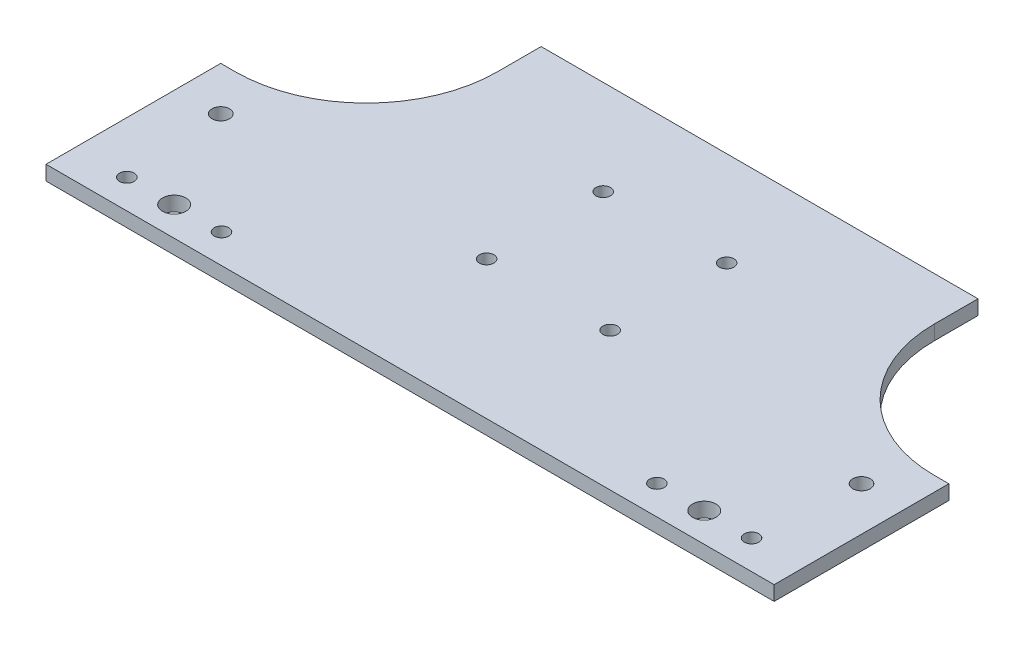
SolidWorks part; units mm, degrees
ref_plane "Front Plane" through (0, 0, 0) normal (0, 0, 1) x (1, 0, 0)
ref_plane "Top Plane" through (0, 0, 0) normal (0, 1, 0) x (1, 0, 0)
ref_plane "Right Plane" through (0, 0, 0) normal (1, 0, 0) x (0, 0, -1)
sketch "Sketch1" plane through (0, 0, 0) normal (0, 1, 0) x (1, 0, 0)
  line L0 (0, 0) -> (0, 64.2675) construction
  line L1 (-125, -45) -> (125, -45)
  line L2 (-125, -45) -> (-125, 15)
  line L3 (-125, 15) -> (125, 15) construction
  line L4 (125, -45) -> (125, 15)
  line L5 (0, 15) -> (0, -45) construction
  line L6 (-75, 60) -> (-75, 75)
  line L7 (-75, 75) -> (0, 75)
  line L8 (-125, 15) -> (-120, 15)
  line L9 (0, 75) -> (75, 75)
  line L10 (75, 75) -> (75, 60)
  line L11 (120, 15) -> (125, 15)
  circle A0 centre (-91, -35) radius 4
  circle A1 centre (91, -35) radius 4
  arc A2 (75, 60) -> (120, 15) centre (120, 60) ccw
  arc A3 (-75, 60) -> (-120, 15) centre (-120, 60) cw
  point P0 (0, 0)
  point P23 (-75, 15)
  dimension "D6" = 8
  dimension "D7" = 60
  dimension "D10" = 45
  dimension "D1" = 250
  dimension "D2" = 60
  dimension "D3" = 91
  dimension "D4" = 125
  dimension "D5" = 10
  dimension "D8" = 75
  dimension "D9" = 75
extrude "Boss-Extrude1" add sketch "Sketch1" along normal blind 5
sketch "Sketch2" plane through (0, 0, 0) normal (0, -1, 0) x (1, 0, 0)
  circle A0 centre (110, 0) radius 3
  circle A1 centre (74.75, 35) radius 2.5
  circle A2 centre (107.25, 35) radius 2.5
  circle A3 centre (-110, 0) radius 3
  circle A4 centre (-74.75, 35) radius 2.5
  circle A5 centre (-107.25, 35) radius 2.5
  circle A6 centre (-21.2, -2.5) radius 2.5
  circle A7 centre (21.2, -2.5) radius 2.5
  circle A8 centre (-21.2, -42.5) radius 2.5
  circle A9 centre (21.2, -42.5) radius 2.5
  dimension "D1" = 5
  dimension "D2" = 6
  dimension "D3" = 6
  dimension "D4" = 5
  dimension "D5" = 5
  dimension "D6" = 5
  dimension "D7" = 5
  dimension "D8" = 5
  dimension "D9" = 5
  dimension "D10" = 5
extrude "Cut-Extrude1" cut sketch "Sketch2" against normal blind 10
